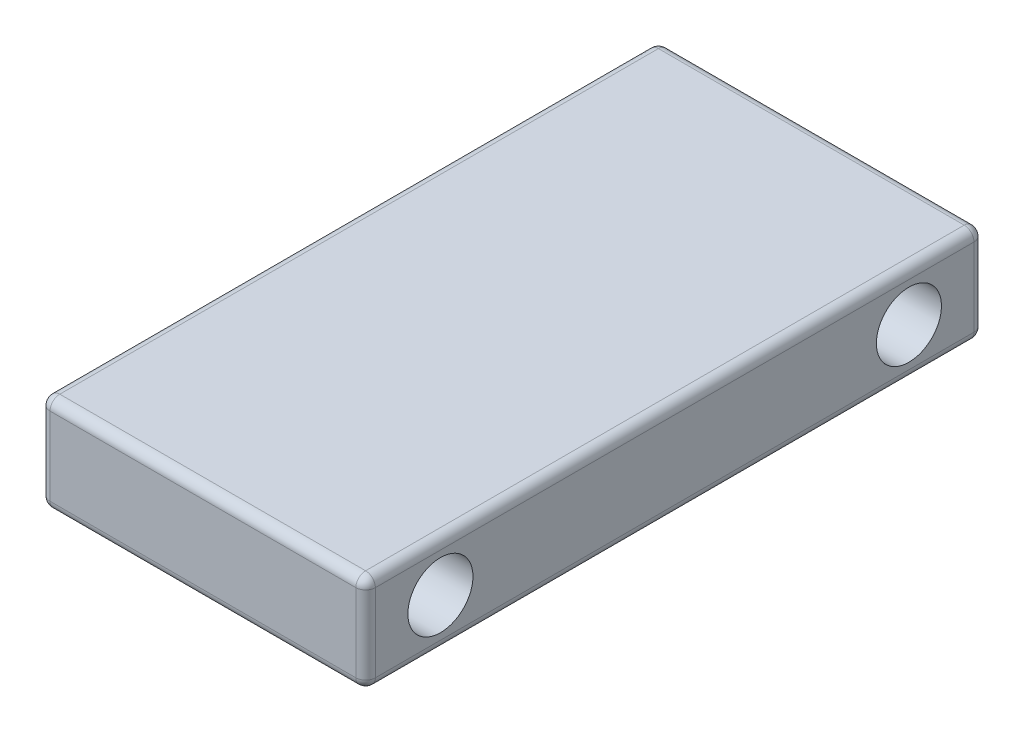
SolidWorks part; units mm, degrees
ref_plane "Front Plane" through (0, 0, 0) normal (0, 0, 1) x (1, 0, 0)
ref_plane "Top Plane" through (0, 0, 0) normal (0, 1, 0) x (1, 0, 0)
ref_plane "Right Plane" through (0, 0, 0) normal (1, 0, 0) x (0, 0, -1)
sketch "Sketch2" plane through (0, 0, 0) normal (0, 1, 0) x (1, 0, 0)
  line L1 (-254, 482.6) -> (254, 482.6)
  line L2 (-254, 482.6) -> (-254, -482.6)
  line L3 (-254, -482.6) -> (254, -482.6)
  line L4 (254, 482.6) -> (254, -482.6)
  line L5 (-254, 482.6) -> (254, -482.6) construction
  line L6 (-254, -482.6) -> (254, 482.6) construction
  point P0 (0, 0)
  point P6 (0, 482.6)
  dimension "D1" = 965.2
  dimension "D2" = 508
extrude "Boss-Extrude1" add sketch "Sketch2" along normal blind 152.4
fillet "Fillet1" radius 15.24 4 edges at (-254, 152.4, 0) (0, 152.4, 482.6) (254, 152.4, 0) (0, 152.4, -482.6)
fillet "Fillet2" radius 15.24 12 edges at (-249.5363, 147.9363, 478.1363) (-249.5363, 147.9363, -478.1363) (249.5363, 147.9363, -478.1363) (254, 68.58, 482.6) (0, 0, -482.6) (-254, 0, 0) (0, 0, 482.6) (254, 0, 0) (-254, 68.58, 482.6) (-254, 68.58, -482.6) (254, 68.58, -482.6) (249.5363, 147.9363, 478.1363)
sketch "Sketch5" plane through (-254, 0, 0) normal (-1, 0, 0) x (0, 0, 1)
  line L0 (0, 0) -> (0, 372.5447) construction
  line L5 (-467.36, 137.16) -> (-467.36, 15.24) construction
  line L6 (-467.36, 152.4) -> (467.36, 152.4) construction
  circle A0 centre (-365.76, 76.2) radius 50.8
  circle A2 centre (365.76, 76.2) radius 50.8
  dimension "D1" = 101.6
  dimension "D2" = 76.2
  dimension "D3" = 101.6
extrude "Cut-Extrude1" cut sketch "Sketch5" against normal through all
